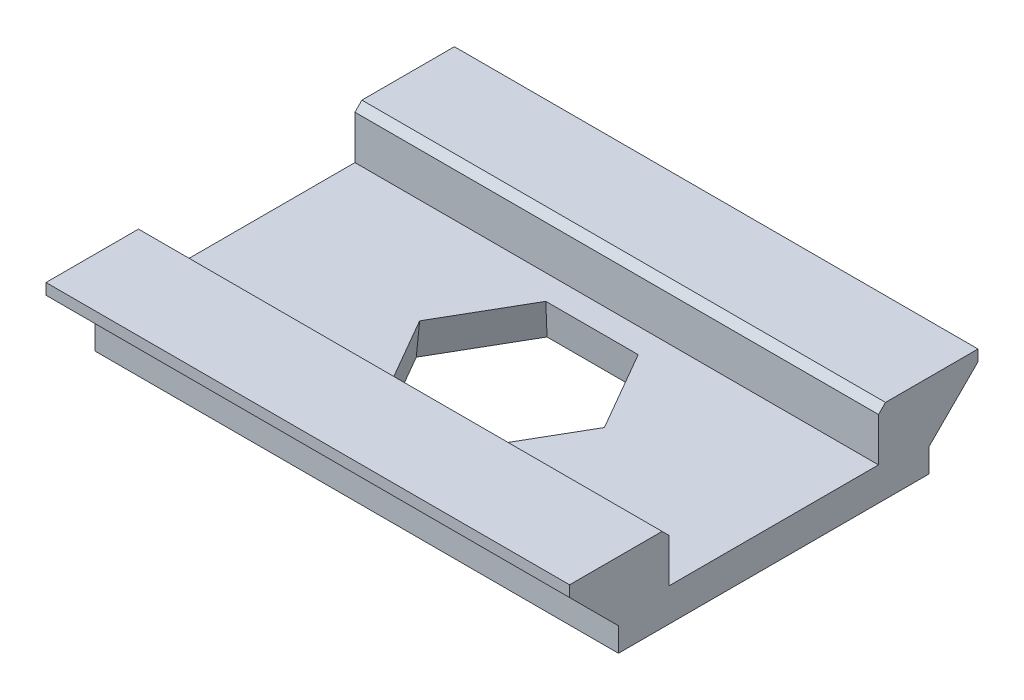
SolidWorks part; units mm, degrees
ref_plane "Front Plane" through (0, 0, 0) normal (0, 0, 1) x (1, 0, 0)
ref_plane "Top Plane" through (0, 0, 0) normal (0, 1, 0) x (1, 0, 0)
ref_plane "Right Plane" through (0, 0, 0) normal (1, 0, 0) x (0, 0, -1)
sketch "Retainer Profile" plane through (0, 0, 0) normal (1, 0, 0) x (0, 0, -1)
  line L1 (-4.65, 2.7923) -> (-4.65, 2.1923) construction
  line L2 (-6.05, 4.1923) -> (-4.65, 2.7923) construction
  line L8 (-6.05, 4.7923) -> (-6.05, 4.1923) construction
  line L9 (-5.05, 4.7923) -> (-6.05, 4.7923) construction
  line L10 (-4.65, 2.7923) -> (-4.65, 2.1923) construction
  line L11 (-6.05, 4.1923) -> (-4.65, 2.7923) construction
  line L23 (0, -28.6883) -> (0, 28.6883) construction
  line L24 (0, -28.6883) -> (0, 28.6883) construction
  line L27 (-6.05, 4.7923) -> (-6.05, 4.1923) construction
  line L28 (-5.05, 4.7923) -> (-6.05, 4.7923) construction
  line L31 (-5.05, 4.5923) -> (-5.85, 4.5923)
  line L32 (-5.85, 4.5923) -> (-5.85, 4.2751)
  line L33 (-5.85, 4.2751) -> (-4.45, 2.8751)
  line L34 (-4.45, 2.8751) -> (-4.45, 2.1923)
  line L35 (-5.05, 4.5923) -> (-3, 4.5923)
  line L36 (-3, 4.5923) -> (-3, 3.1423)
  line L37 (-3, 3.1423) -> (3, 3.1423)
  line L38 (-4.45, 2.1923) -> (4.45, 2.1923)
  line L39 (3, 4.5923) -> (3, 3.1423)
  line L40 (5.05, 4.5923) -> (3, 4.5923)
  line L41 (4.45, 2.8751) -> (4.45, 2.1923)
  line L42 (5.85, 4.2751) -> (4.45, 2.8751)
  line L43 (5.85, 4.5923) -> (5.85, 4.2751)
  line L44 (5.05, 4.5923) -> (5.85, 4.5923)
  point P15 (0, 2.1923)
  point P16 (0, 3.1423)
  dimension "D3" = 3
  dimension "D1" = 0.2
  dimension "D2" = 1.45
extrude "Boss-Extrude1" add sketch "Retainer Profile" along normal mid plane 15
sketch "Sketch3" plane through (0, 4.5923, 0) normal (0, 1, 0) x (1, 0, 0)
  line L1 (2.5, 0) -> (1.25, 2.1651)
  line L2 (1.25, 2.1651) -> (-1.25, 2.1651)
  line L3 (-1.25, 2.1651) -> (-2.5, 0)
  line L4 (-2.5, 0) -> (-1.25, -2.1651)
  line L5 (-1.25, -2.1651) -> (1.25, -2.1651)
  line L6 (1.25, -2.1651) -> (2.5, 0)
  circle A0 centre (0, 0) radius 2.1651 construction
  dimension "D1" = 5
extrude "Cut-Extrude2" cut sketch "Sketch3" against normal through all draft 5 draft outward yes
chamfer "Chamfer1" distance 0.2 angle 45 2 edges at (0, 4.5923, 3) (0, 4.5923, -3)
